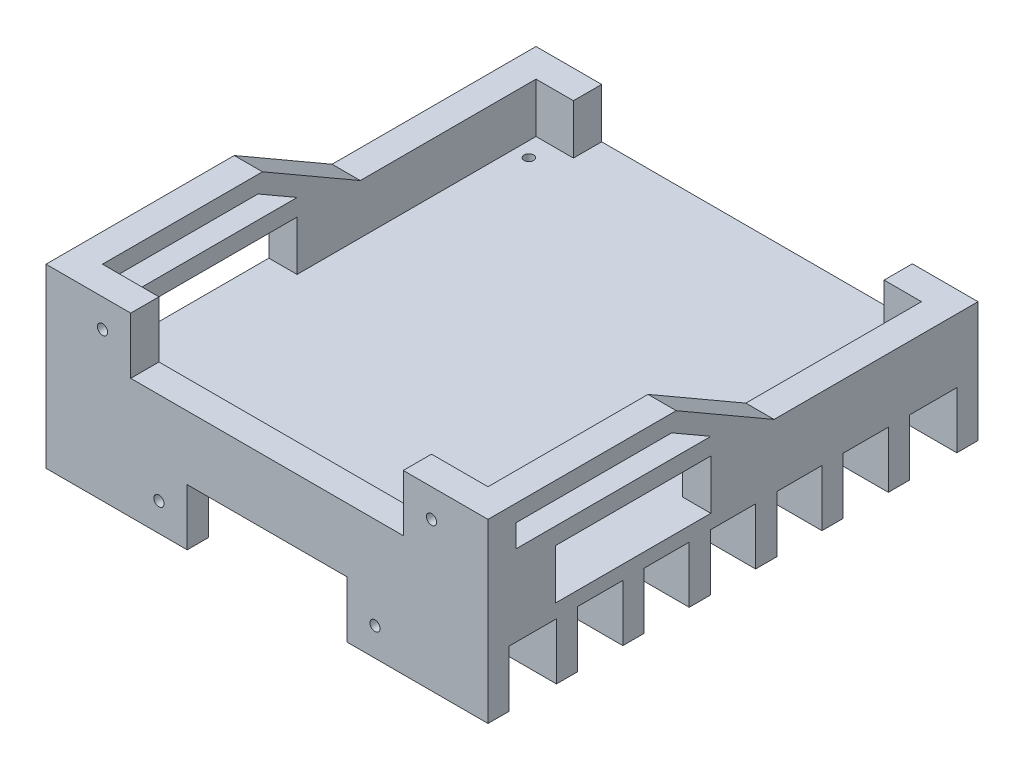
SolidWorks part; units mm, degrees
note: The reader was unsure of these and kept them because the rebuilt part matched: shared geometry of "Sketch1<2>".
ref_plane "Front Plane" through (0, 0, 0) normal (0, 0, 1) x (1, 0, 0)
ref_plane "Top Plane" through (0, 0, 0) normal (0, 1, 0) x (1, 0, 0)
ref_plane "Right Plane" through (0, 0, 0) normal (1, 0, 0) x (0, 0, -1)
sketch "Sketch1" plane through (0, 0, 0) normal (0, 1, 0) x (1, 0, 0)
  line L0 (-68, -76.5) -> (-68, 76.5) construction
  line L1 (-68, -76.5) -> (68, -76.5) construction
  line L2 (-68, 76.5) -> (68, 76.5) construction
  line L3 (68, -76.5) -> (68, 76.5) construction
  line L4 (-68, -76.5) -> (68, 76.5) construction
  line L5 (-68, 76.5) -> (68, -76.5) construction
  line L6 (-68.25, -76.75) -> (-68.25, 76.75)
  line L7 (-68.25, 76.75) -> (68.25, 76.75)
  line L8 (68.25, -76.75) -> (68.25, 76.75)
  line L9 (-68.25, -76.75) -> (68.25, -76.75)
  line L10 (-78.25, -86.75) -> (-78.25, 86.75)
  line L11 (-78.25, 86.75) -> (78.25, 86.75)
  line L12 (78.25, -86.75) -> (78.25, 86.75)
  line L13 (-78.25, -86.75) -> (78.25, -86.75)
  line L14 (-68.25, -62.85) -> (-78.25, -62.85)
  line L15 (-68.25, -7.85) -> (-78.25, -7.85)
  line L16 (0, -34.43) -> (0, 34.43) construction
  line L17 (68.25, -7.85) -> (78.25, -7.85)
  line L18 (68.25, -62.85) -> (78.25, -62.85)
  line L19 (-55, 76.75) -> (-55, 86.75)
  line L20 (55, 76.75) -> (55, 86.75)
  point P1 (0, 0)
  point P28 (-55, 81.75)
  point P29 (-55, 76.75)
  dimension "D1" = 136
  dimension "D2" = 153
  dimension "D4" = 10
  dimension "D5" = 62.85
  dimension "D6" = 55
  dimension "D7" = 110
  dimension "D3" = 0.25
extrude "Boss-Extrude1" add sketch "Sketch1" against normal blind 5 contours L8 L17 L12 L11 L10 L15 L6 L7 | L9 L20 L13 L12 L18 L8 | L19 L9 L6 L14 L10 L13 | L20 L7 L8 L17 L12 L11 | L7 L19 L11 L10 L15 L6 | L8 L18 L12 L17 | L6 L9 L8 L7
extrude "Boss-Extrude2" add sketch "Sketch1<2>" along normal blind 17.6 contours L7 L19 L11 L10 L15 L6 | L20 L7 L8 L17 L12 L11 | L18 L8 L9 L6 L14 L10 L13 L12
sketch "Sketch1<2>" plane through (0, 0, 0) normal (0, 1, 0) x (1, 0, 0) same geometry as "Sketch1"
sketch "Sketch2" plane through (0, 0, 0) normal (0, 1, 0) x (1, 0, 0)
  line L0 (0, -30.25) -> (0, 30.25) construction
  point P0 (-63, 69)
  point P1 (-63, -70.35)
  point P2 (0, 0)
  point P4 (0, 0)
  point P7 (63, -70.35)
  point P8 (63, 69)
  point P9 (0, 0)
  dimension "D1" = 70.35
  dimension "D2" = 126
  dimension "D3" = 139.35
hole_wizard "M3 Clearance Hole1" positions "Sketch2" profile "Sketch3" hole size "M3" standard "ANSI Metric" end condition through all
sketch "Sketch3" plane through (-63, 0, -69) normal (1, 0, 0) x (0, 0, 1)
  line L0 (0, 0) -> (0, 5)
  line L1 (0, 5) -> (1.7, 5)
  line L2 (1.7, 5) -> (1.7, 0)
  line L5 (1.7, 0) -> (0, 0)
  line L11 (0, -6.35) -> (0, 107.95) construction
  dimension "Thru Hole Dia." = 3.4
  dimension "Thru Hole Depth" = 5
sketch "Sketch6" plane through (0, -5, 0) normal (0, -1, 0) x (1, 0, 0)
  line L0 (-78.25, 86.75) -> (-78.25, -86.75) construction
  line L1 (-78.25, 86.75) -> (-28.25, 86.75)
  line L2 (-78.25, 86.75) -> (-78.25, 79.25)
  line L3 (-78.25, 79.25) -> (-28.25, 79.25)
  line L4 (-28.25, 86.75) -> (-28.25, 79.25)
  line L5 (-78.25, 62.5) -> (-28.25, 62.5)
  line L6 (-78.25, 62.5) -> (-78.25, 55)
  line L7 (-78.25, 55) -> (-28.25, 55)
  line L8 (-28.25, 62.5) -> (-28.25, 55)
  line L9 (-78.25, 39) -> (-78.25, 31.5)
  line L10 (-78.25, 39) -> (-28.25, 39)
  line L11 (-28.25, 39) -> (-28.25, 31.5)
  line L12 (-78.25, 31.5) -> (-28.25, 31.5)
  line L13 (-78.25, 15.5) -> (-78.25, 8)
  line L14 (-78.25, 15.5) -> (-28.25, 15.5)
  line L15 (-28.25, 15.5) -> (-28.25, 8)
  line L16 (-78.25, 8) -> (-28.25, 8)
  line L17 (-78.25, 62.5) -> (-78.25, 39) construction
  line L18 (0, -30.25) -> (0, 30.25) construction
  line L19 (78.25, 15.5) -> (28.25, 15.5)
  line L20 (28.25, 15.5) -> (28.25, 8)
  line L21 (78.25, 8) -> (28.25, 8)
  line L22 (78.25, 15.5) -> (78.25, 8)
  line L23 (78.25, 39) -> (28.25, 39)
  line L24 (28.25, 39) -> (28.25, 31.5)
  line L25 (78.25, 31.5) -> (28.25, 31.5)
  line L26 (78.25, 39) -> (78.25, 31.5)
  line L27 (78.25, 55) -> (28.25, 55)
  line L28 (28.25, 62.5) -> (28.25, 55)
  line L29 (78.25, 62.5) -> (28.25, 62.5)
  line L30 (78.25, 62.5) -> (78.25, 55)
  line L31 (78.25, 79.25) -> (28.25, 79.25)
  line L32 (28.25, 86.75) -> (28.25, 79.25)
  line L33 (78.25, 86.75) -> (28.25, 86.75)
  line L34 (78.25, 86.75) -> (78.25, 79.25)
  line L35 (30.25, 0) -> (-30.25, 0) construction
  line L37 (78.25, -86.75) -> (78.25, -79.25)
  line L38 (78.25, -86.75) -> (28.25, -86.75)
  line L39 (28.25, -86.75) -> (28.25, -79.25)
  line L40 (78.25, -79.25) -> (28.25, -79.25)
  line L41 (78.25, -62.5) -> (78.25, -55)
  line L42 (78.25, -62.5) -> (28.25, -62.5)
  line L43 (28.25, -62.5) -> (28.25, -55)
  line L44 (78.25, -55) -> (28.25, -55)
  line L45 (78.25, -39) -> (78.25, -31.5)
  line L46 (78.25, -31.5) -> (28.25, -31.5)
  line L47 (28.25, -39) -> (28.25, -31.5)
  line L48 (78.25, -39) -> (28.25, -39)
  line L49 (78.25, -15.5) -> (78.25, -8)
  line L50 (78.25, -8) -> (28.25, -8)
  line L51 (28.25, -15.5) -> (28.25, -8)
  line L52 (78.25, -15.5) -> (28.25, -15.5)
  line L53 (-78.25, -8) -> (-28.25, -8)
  line L54 (-28.25, -15.5) -> (-28.25, -8)
  line L55 (-78.25, -15.5) -> (-28.25, -15.5)
  line L56 (-78.25, -15.5) -> (-78.25, -8)
  line L57 (-78.25, -31.5) -> (-28.25, -31.5)
  line L58 (-28.25, -39) -> (-28.25, -31.5)
  line L59 (-78.25, -39) -> (-28.25, -39)
  line L60 (-78.25, -39) -> (-78.25, -31.5)
  line L61 (-28.25, -62.5) -> (-28.25, -55)
  line L62 (-78.25, -55) -> (-28.25, -55)
  line L63 (-78.25, -62.5) -> (-78.25, -55)
  line L64 (-78.25, -62.5) -> (-28.25, -62.5)
  line L65 (-28.25, -86.75) -> (-28.25, -79.25)
  line L66 (-78.25, -79.25) -> (-28.25, -79.25)
  line L67 (-78.25, -86.75) -> (-78.25, -79.25)
  line L68 (-78.25, -86.75) -> (-28.25, -86.75)
  line L69 (-78.25, 31.5) -> (-78.25, 15.5) construction
  line L70 (-78.25, 8) -> (-78.25, -8) construction
  circle A0 centre (-63, 70.35) radius 2.75 construction
  circle A1 centre (-63, -69) radius 2.75 construction
  dimension "D2" = 5.5
  dimension "D3" = 7.5
  dimension "D4" = 50
  dimension "D5" = 180
  dimension "D6" = 180
  dimension "D7" = 16
  dimension "D1" = 3
extrude "Boss-Extrude3" add sketch "Sketch6" along normal blind 20
sketch "Sketch7" plane through (78.25, 0, 0) normal (1, 0, 0) x (0, 0, -1)
  line L0 (-86.75, 17.6) -> (-86.75, 37.6)
  line L1 (-86.75, 37.6) -> (-20.0987, 37.6)
  line L2 (-20.0987, 37.6) -> (14.5423, 17.6)
  line L3 (-7.85, 17.6) -> (86.75, 17.6) construction
  line L4 (14.5423, 17.6) -> (-86.75, 17.6)
  line L11 (-76.75, 31.6) -> (-21.7064, 31.6)
  line L12 (-21.7064, 31.6) -> (-7.85, 23.6)
  line L13 (-7.85, 23.6) -> (-76.75, 23.6)
  line L14 (-86.75, 31.6) -> (-21.7064, 31.6) construction
  line L15 (-7.85, 23.6) -> (-86.75, 23.6) construction
  line L16 (-7.85, 17.6) -> (-7.85, 0) construction
  line L17 (-76.75, 31.6) -> (-76.75, 23.6)
  line L18 (-76.75, 17.6) -> (-76.75, 0) construction
  point P11 (0, 0)
  dimension "D2" = 30
  dimension "D3" = 20
  dimension "D1" = 6
extrude "Boss-Extrude5" add sketch "Sketch7" against normal up to surface (10 mm away) up to face at (68.25, 8.8, -34.45)
sketch "Sketch8" plane through (0, 0, 86.75) normal (0, 0, 1) x (1, 0, 0)
  line L0 (68.25, 37.6) -> (78.25, 37.6) construction
  line L1 (68.25, 17.6) -> (48.25, 17.6)
  line L2 (68.25, 17.6) -> (68.25, 37.6)
  line L3 (68.25, 37.6) -> (48.25, 37.6)
  line L4 (48.25, 17.6) -> (48.25, 37.6)
  line L5 (48.25, 37.6) -> (68.25, 17.6) construction
  circle A0 centre (58.25, 27.6) radius 1.8
  dimension "D1" = 3.6
extrude "Boss-Extrude6" add sketch "Sketch8" against normal up to surface (10 mm away) up to face at (0, 8.8, 76.75)
mirror "Mirror2" about plane through (0, 0, 0) normal (1, 0, 0) of bodies 110
sketch "Sketch9" plane through (0, 0, 79.25) normal (0, 0, -1) x (-1, 0, 0)
  line L0 (-28.25, -15) -> (-38.25, -15) construction
  line L1 (-28.25, -25) -> (-28.25, -5) construction
  line L2 (-38.25, -15) -> (-38.25, -25) construction
  line L3 (-28.25, -25) -> (-78.25, -25) construction
  line L4 (0, 30.25) -> (0, -30.25) construction
  circle A0 centre (-38.25, -15) radius 1.8
  circle A1 centre (38.25, -15) radius 1.8
  dimension "D1" = 3.6
extrude "Cut-Extrude1" cut sketch "Sketch9" against normal through all
